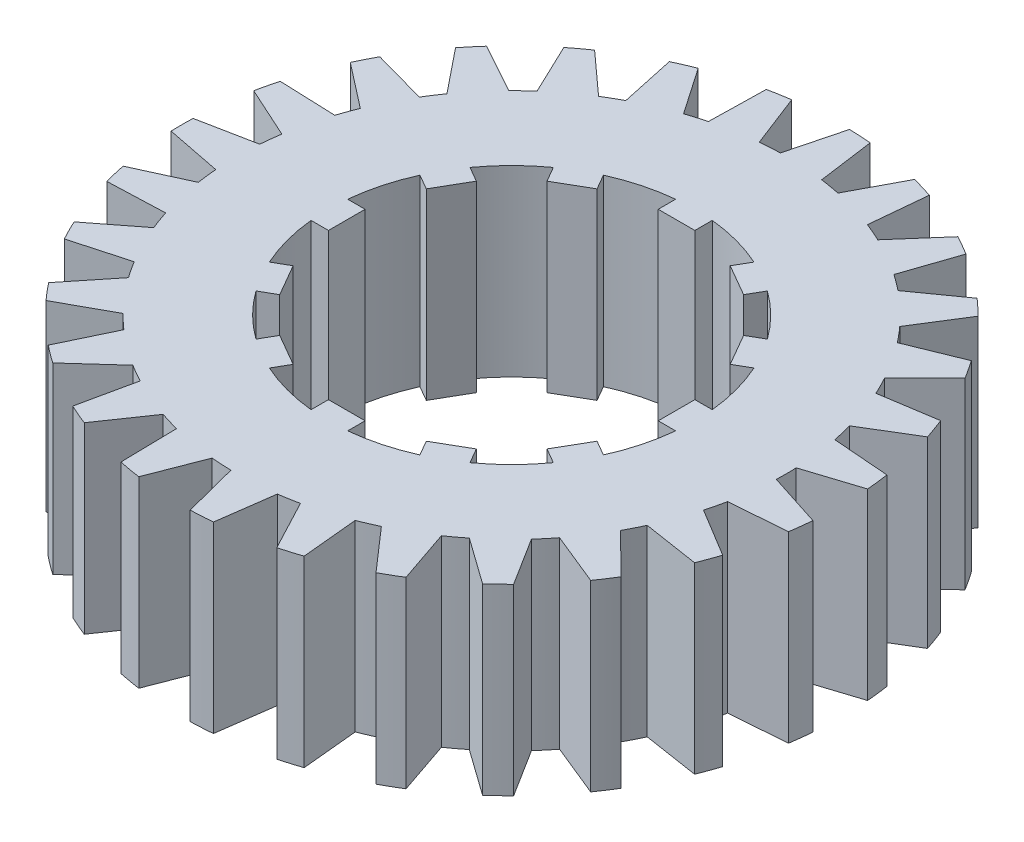
SolidWorks part; units mm, degrees
material "AISI 8620 Steel, carburized"
ref_plane "Front Plane" through (0, 0, 0) normal (1, 0, 0) x (0, 1, 0)
ref_plane "Top Plane" through (0, 0, 0) normal (0, 0, 1) x (0, 1, 0)
ref_plane "Right Plane" through (0, 0, 0) normal (0, 1, 0) x (-1, 0, 0)
sketch "Sketch1" plane through (0, 0, 0) normal (0, 1, 0) x (-1, 0, 0)
  line L0 (0, 20.6567) -> (0, -19.5215) construction
  line L1 (-20.581, 0) -> (20.7451, 0) construction
  line L3 (-1, 10) -> (1, 10)
  line L4 (-1, 10) -> (-1, 9)
  line L5 (-1, 9) -> (1, 9)
  line L6 (1, 10) -> (1, 9)
  line L7 (17.99, 0.6) -> (14.9519, 1.2)
  line L8 (17.99, -0.6) -> (14.9519, -1.2)
  circle A0 centre (0, 0) radius 15
  circle A1 centre (0, 0) radius 10
  arc A2 (0, 18) -> (0, -18) centre (0, 0) ccw
  arc A3 (17.99, -0.6) -> (17.99, 0.6) centre (0, 0) ccw
  point P13 (0, 10)
  dimension "D2" = 30
  dimension "D7" = 2.4
  dimension "D8" = 18
  dimension "D3" = 2
  dimension "D4" = 1
  dimension "D5" = 0.6
  dimension "D6" = 1.2
  dimension "D1" = 5
extrude "Boss-Extrude1" add sketch "Sketch1" along normal mid plane 10 contours A0 A1 L4 L3 L6 | A1 L6 L3 | A1 L3 L4 region at (0.7501, 0, 9.985) region at (-0.7501, 0, 9.985) region at (-14.5641, 0, 0.5835)
extrude "Boss-Extrude2" add sketch "Sketch1<3>" along normal mid plane 10 contours A0 L8 A3 L7 region at (-16.3237, 0, 0)
sketch "Sketch1<3>" plane through (0, 0, 0) normal (0, 1, 0) x (-1, 0, 0) same geometry as "Sketch1"
extrude "Boss-Extrude3" add sketch "Sketch1<4>" along normal mid plane 10 contours A1 L4 L5 L6 region at (0, 0, 9.4918)
sketch "Sketch1<4>" plane through (0, 0, 0) normal (0, 1, 0) x (-1, 0, 0) same geometry as "Sketch1"
pattern_circular "CirPattern1" count 12 over 360 about axis through (0, 5, 0) along (0, 1, 0) of "Boss-Extrude3"
pattern_circular "CirPattern2" count 27 over 360 about axis through (0, -5, 0) along (0, 1, 0) of "Boss-Extrude2"
ref_axis "Axis1" through (0, -0.5, 0) along (0, 1, 0)
